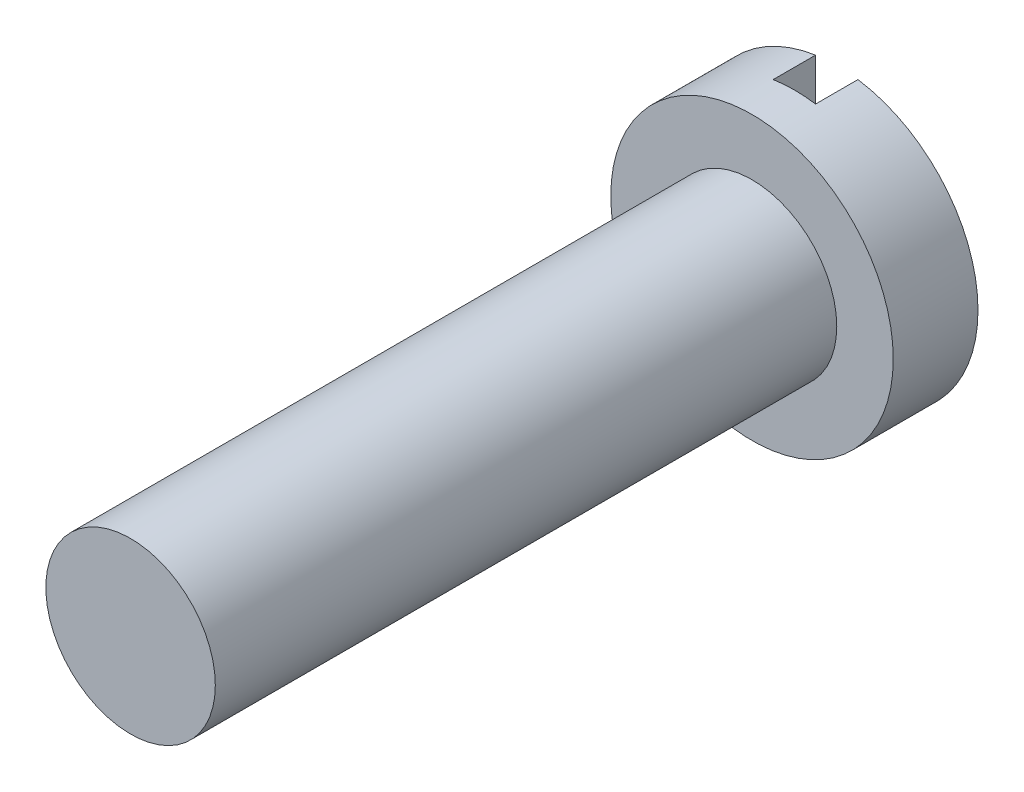
SolidWorks part; units mm, degrees
ref_plane "前视基准面" through (0, 0, 0) normal (0, 0, 1) x (1, 0, 0)
ref_plane "上视基准面" through (0, 0, 0) normal (0, 1, 0) x (1, 0, 0)
ref_plane "右视基准面" through (0, 0, 0) normal (1, 0, 0) x (0, 0, -1)
sketch "草图1" plane through (0, 0, 0) normal (0, 0, 1) x (1, 0, 0)
  circle A0 centre (0, 0) radius 3
  circle A1 centre (0, 0) radius 5
  dimension "D1" = 6
  dimension "D2" = 10
extrude "凸台-拉伸1" add sketch "草图1" along normal blind 22 contours A0 region at (0, 0, 0)
cosmetic thread "装饰螺纹线1" parameters "D1"=6, "D2"=5
extrude "凸台-拉伸2" add sketch "草图1<3>" against normal blind 3 contours A0 | A1 A0 region at (0, 0, 0) region at (-4.8586, 0, 0)
sketch "草图1<3>" plane through (0, 0, 0) normal (0, 0, 1) x (1, 0, 0) same geometry as "草图1"
sketch "草图2" plane through (0, 0, -3) normal (0, 0, -1) x (-1, 0, 0)
  line L0 (0, 0) -> (0, 5) construction
  line L1 (0, 0) -> (0, -5) construction
  line L3 (0.75, -5) -> (-0.75, -5)
  line L4 (0.75, -5) -> (0.75, 5)
  line L5 (0.75, 5) -> (-0.75, 5)
  line L6 (-0.75, -5) -> (-0.75, 5)
  line L7 (0.75, -5) -> (-0.75, 5) construction
  line L8 (0.75, 5) -> (-0.75, -5) construction
  circle A0 centre (0, 0) radius 5 construction
  dimension "D1" = 1.5
extrude "切除-拉伸1" cut sketch "草图2" against normal blind 1.5
